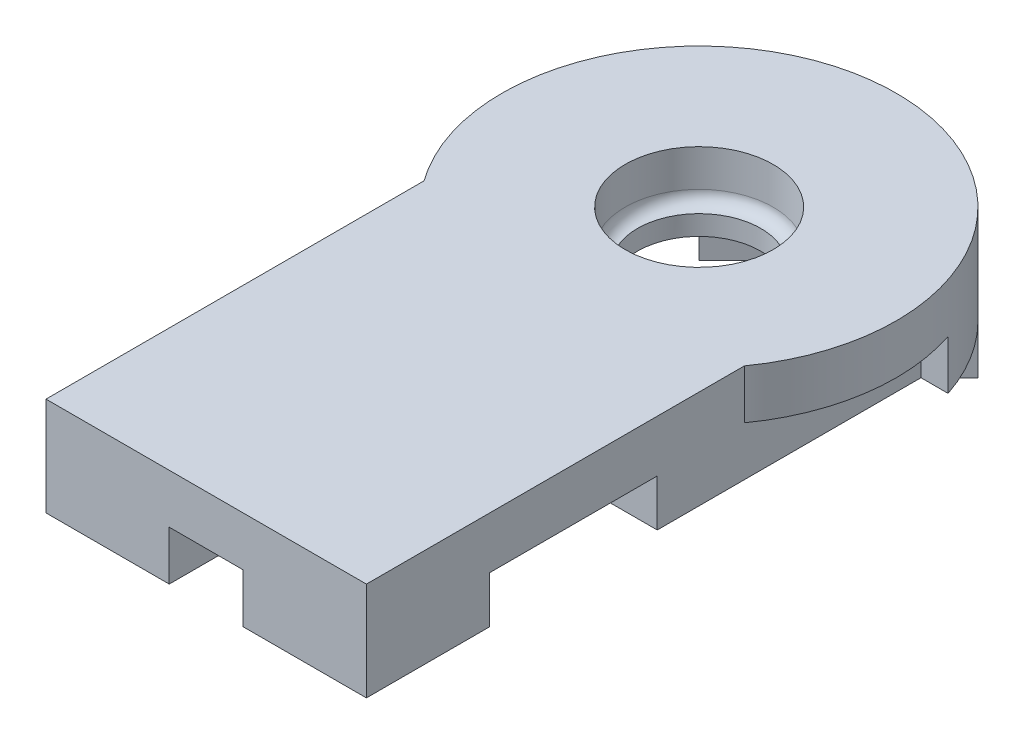
SolidWorks part; units mm, degrees
ref_plane "Front Plane" through (0, 0, 0) normal (0, 0, 1) x (1, 0, 0)
ref_plane "Top Plane" through (0, 0, 0) normal (0, 1, 0) x (1, 0, 0)
ref_plane "Right Plane" through (0, 0, 0) normal (1, 0, 0) x (0, 0, -1)
sketch "Sketch1" plane through (0, 0, 0) normal (0, 1, 0) x (1, 0, 0)
  line L0 (-996.0269, -20) -> (49003.9731, -20) construction
  line L3 (-6.5, -20) -> (6.5, -20)
  line L4 (6.5, -1010) -> (6.5, -4.6637) construction
  line L5 (-6.5, -1010) -> (-6.5, -4.6637) construction
  line L6 (6.5, -4.6637) -> (6.5, -20)
  line L7 (-6.5, -4.6637) -> (-6.5, -20)
  line L8 (-6.5, 4.6637) -> (-6.5, 48990) construction
  line L9 (6.5, 4.6637) -> (6.5, 48990) construction
  arc A0 (6.5, 4.6637) -> (-6.5, 4.6637) centre (0, 0) ccw
  arc A1 (-8, 0) -> (8, 0) centre (0, 0) ccw construction
  arc A2 (-6.5, 4.6637) -> (-8, 0) centre (0, 0) ccw construction
  arc A3 (8, 0) -> (6.5, 4.6637) centre (0, 0) ccw construction
  arc A4 (-6.5, 4.6637) -> (-6.5, -4.6637) centre (0, 0) ccw
  arc A5 (6.5, 4.6637) -> (6.5, -4.6637) centre (0, 0) cw
  dimension "D1" = 16
  dimension "D2" = 20
  dimension "D3" = 6.5
  dimension "D4" = 6.5
extrude "Boss-Extrude1" add sketch "Sketch1" against normal blind 4
sketch "Sketch2" plane through (0, 0, 0) normal (0, 1, 0) x (1, 0, 0)
  circle A1 centre (0, 0) radius 2.5
  dimension "D1" = 5
extrude "Cut-Extrude1" cut sketch "Sketch2" against normal through all
sketch "Sketch3" plane through (0, 0, 0) normal (0, 1, 0) x (1, 0, 0)
  circle A0 centre (0, 0) radius 3
extrude "Cut-Extrude2" cut sketch "Sketch3" against normal blind 2
sketch "Sketch4" plane through (0, -4, 0) normal (0, -1, 0) x (1, 0, 0)
  line L0 (0, 0) -> (0, -5.75) construction
  line L1 (2.5, -5.75) -> (-2.5, -5.75)
  line L2 (5.75, 0) -> (-5.75, 0) construction
  line L3 (5.75, -1000) -> (5.75, 49000) construction
  line L4 (-5.75, -1000) -> (-5.75, 49000) construction
  line L5 (2.5, -5.75) -> (5.75, -2.5)
  line L6 (5.75, -2.5) -> (5.75, 6.25)
  line L7 (-2.5, -5.75) -> (-5.75, -2.5)
  line L8 (-5.75, -2.5) -> (-5.75, 6.25)
  line L9 (-755.7679, 8.2) -> (49244.2321, 8.2) construction
  line L10 (2.9, 8.2) -> (2.1, 8.2) construction
  line L12 (-5.75, 6.25) -> (-4.4, 6.25)
  line L13 (-5.5, 6.5) -> (5.5, 6.5) construction
  line L14 (-4.4, 6.25) -> (-4.4, 8.2)
  line L15 (-6.5, 20) -> (6.5, 20) construction
  line L16 (-2.9, 6.8941) -> (-2.9, 8.2) construction
  line L18 (-6.5, 20) -> (6.5, 20) construction
  line L19 (6.5, 10) -> (6.5, 8.2)
  line L21 (-4.4, 6.25) -> (4.4, 6.25) construction
  line L22 (4.4, 6.25) -> (5.75, 6.25)
  line L23 (4.4, 8.2) -> (5.6604, 10) construction
  line L24 (-4.4, 8.2) -> (-5.6604, 10)
  line L25 (4.4, 8.2) -> (4.4, 20) construction
  line L26 (-4.4, 8.2) -> (-4.4, 20) construction
  line L27 (6.5, 11.1991) -> (6.5, 15)
  line L31 (-6.5, 11.1991) -> (-6.5, 15)
  line L33 (-6.5, 15) -> (-6.5, 20.6628) construction
  line L34 (-1005.75, -2.5) -> (48994.25, -2.5) construction
  line L35 (-999.9505, 10) -> (49000.0495, 10) construction
  line L36 (6.5, 11.1991) -> (6.5, 10)
  line L37 (-6.5, 15) -> (6.5, 15)
  line L39 (6.5, 15) -> (6.5, 20.6628) construction
  line L40 (6.5, 20) -> (6.5, 4.6637) construction
  line L41 (6.5, 10) -> (5.6604, 10) construction
  line L42 (5.75, 10.128) -> (6.5, 11.1991) construction
  line L43 (5.6604, 10) -> (5.75, 10.128) construction
  line L44 (-6.5, 11.1991) -> (-6.5, 10)
  line L45 (-6.5, 4.6637) -> (-6.5, 20) construction
  line L46 (-6.5, 10) -> (-5.6604, 10)
  line L47 (-5.6604, 10) -> (-5.75, 10.128) construction
  line L48 (-5.75, 10.128) -> (-6.5, 11.1991) construction
  line L49 (4.4, 8.2) -> (4.4, 6.25)
  line L50 (-6.5, 20) -> (6.5, 20) construction
  line L51 (6.5, 8.2) -> (4.4, 8.2)
  point P6 (0, -5.75)
  point P9 (0, 0)
  circle M8 centre (0, 0) radius 2.5
  line M20 (6.5, 4.6637) -> (6.5, 20)
  line M21 (-6.5, 20) -> (-6.5, 4.6637)
  dimension "D3" = 0.25
  dimension "D1" = 5.75
  dimension "D2" = 11.5
  dimension "D4" = 1.5
  dimension "D6" = 2.5
  dimension "D7" = 10
  dimension "D8" = 15
  dimension "D9" = 6.25
  dimension "D10" = 35
  dimension "D11" = 35
extrude "Cut-Extrude3" cut sketch "Sketch4" against normal blind 1.2 contours L46 L24 L14 L12 L8 L7 L1 L5 L6 L22 L49 L23 L41 L37 M21 M20 M8
sketch "Sketch6" plane through (0, -2.8, 0) normal (0, -1, 0) x (1, 0, 0)
  line L0 (6.5, 15) -> (6.5, 8.2)
  line L3 (4.4, 6.2) -> (-4.4, 6.2)
  line L4 (6.5, 8.2) -> (6.5, 15) construction
  line L5 (6.5, 15) -> (-6.5, 15)
  line L6 (-6.5, 15) -> (-6.5, 11.1991)
  line L7 (-5.6604, 10) -> (-4.4, 8.2)
  line L8 (-4.4, 8.2) -> (-4.4, 6.2)
  line L10 (6.5, 8.2) -> (4.4, 8.2)
  line L15 (-5.6604, 10) -> (-4.4, 8.2) construction
  line L16 (-6.5, 11.1991) -> (-6.5, 10)
  line L18 (-6.5, 10) -> (-5.6604, 10)
  line L19 (-6.5, 10) -> (-5.6604, 10) construction
  line L20 (-6.5, 11.1991) -> (-5.6604, 10) construction
  line L21 (4.4, 6.2) -> (4.4, 8.2)
  line L22 (4.4, 8.2) -> (4.4, 6.25) construction
  dimension "D1" = 2
extrude "Cut-Extrude5" cut sketch "Sketch6" against normal blind 0.7
sketch "Sketch7" plane through (0, 0, 20) normal (0, 0, 1) x (1, 0, 0)
  line L1 (-6.5, -4) -> (6.5, -4)
  line L2 (-6.5, -4) -> (-6.5, 0)
  line L3 (-6.5, 0) -> (6.5, 0)
  line L4 (6.5, -4) -> (6.5, 0)
extrude "Cut-Extrude6" [suppressed] cut sketch "Sketch7" against normal up to vertex
sketch "Sketch10" plane through (0, -4, 0) normal (0, -1, 0) x (1, 0, 0)
  line L0 (-6.5, 4.6637) -> (-6.5, -2.5)
  line L1 (6.5, 4.6637) -> (6.5, -2.5)
  line L2 (-1005.75, -2.5) -> (48994.25, -2.5) construction
  line L3 (-6.5, -2.5) -> (-7.5993, -2.5)
  line L4 (-6.5, -2.5) -> (-6.5, -4.6637) construction
  line L5 (6.5, -2.5) -> (7.5993, -2.5)
  line L6 (6.5, -2.5) -> (6.5, -4.6637) construction
  arc A0 (-6.5, 4.6637) -> (6.5, 4.6637) centre (0, 0) ccw construction
  arc A1 (-6.5, 4.6637) -> (-7.5993, -2.5) centre (0, 0) ccw
  arc A2 (6.5, 4.6637) -> (7.5993, -2.5) centre (0, 0) cw
  arc A3 (-7.5993, -2.5) -> (-6.5, -4.6637) centre (0, 0) ccw construction
  arc A4 (7.5993, -2.5) -> (6.5, -4.6637) centre (0, 0) cw construction
  dimension "D1" = 8
  dimension "D2" = 8
extrude "Cut-Extrude8" cut sketch "Sketch10" against normal blind 2
sketch "Sketch11" plane through (0, -4, 0) normal (0, -1, 0) x (1, 0, 0)
  line L0 (0, -1000) -> (0, 49000) construction
  line L1 (-0.75, -1003.313) -> (-0.75, 48996.687) construction
  line L2 (0.75, -1004.6428) -> (0.75, 48995.3572) construction
  line L3 (-0.75, -7.9648) -> (-0.75, -5.75)
  line L4 (-0.75, -5.75) -> (-2.5, -5.75)
  line L6 (0.75, -7.9648) -> (0.75, -5.75)
  line L7 (0.75, -5.75) -> (2.5, -5.75)
  line L9 (-2.5, -5.75) -> (2.5, -5.75) construction
  line L10 (0, 0) -> (35355.3391, -35355.3391) construction
  line L11 (2.5, -5.75) -> (5.75, -2.5) construction
  line L12 (0, 0) -> (-35355.3391, -35355.3391) construction
  line L13 (-5.75, -2.5) -> (-2.5, -5.75) construction
  line L14 (-2.5, -5.75) -> (-4.125, -4.125)
  line L15 (-4.125, -4.125) -> (-5.6569, -5.6569)
  line L16 (2.5, -5.75) -> (4.125, -4.125)
  line L17 (4.125, -4.125) -> (5.6569, -5.6569)
  arc A0 (-7.5993, -2.5) -> (7.5993, -2.5) centre (0, 0) ccw construction
  arc A1 (-5.6569, -5.6569) -> (-0.75, -7.9648) centre (0, 0) ccw
  arc A2 (5.6569, -5.6569) -> (0.75, -7.9648) centre (0, 0) cw
  point P27 (4.125, -4.125)
  point P32 (-4.125, -4.125)
  dimension "D1" = 0.75
  dimension "D2" = 0.75
extrude "Boss-Extrude3" add sketch "Sketch11" along normal blind 2
fillet "Fillet3" radius 0.5 1 edges at (0, -2, 3)
sketch "Sketch12" plane through (0, -4, 0) normal (0, -1, 0) x (1, 0, 0)
  line L0 (0, 20) -> (0, 15) construction
  line L1 (-6.5, 20) -> (6.5, 20) construction
  line L2 (6.5, 15) -> (-6.5, 15) construction
  line L3 (1.5, 15) -> (1.5, 20)
  line L4 (-1.5, 15) -> (-1.5, 20)
  line L5 (-1.5, 20) -> (1.5, 20)
  line L6 (0, 15) -> (-1.5, 15)
  line L7 (1.5, 15) -> (-1.5, 15)
  line L8 (1.5, 15) -> (0, 15) construction
  line M11 (6.5, 20) -> (-6.5, 20)
  dimension "D1" = 1.5
  dimension "D2" = 1.5
  dimension "D3" = 5
extrude "Cut-Extrude9" cut sketch "Sketch12" against normal blind 2 contours L7 L3 L4 M11
sketch "Sketch13" plane through (0, -2.1, 0) normal (0, -1, 0) x (1, 0, 0)
  line L0 (-6.5, 15) -> (-6.5, 10)
  line L1 (-6.5, 10) -> (-5.6604, 10)
  line L2 (-5.6604, 10) -> (-4.4, 8.2)
  line L3 (-4.4, 8.2) -> (-4.4, 15)
  line L4 (-6.5, 15) -> (-1.5, 15) construction
  line L5 (-4.4, 15) -> (-6.5, 15)
extrude "Boss-Extrude4" add sketch "Sketch13" along normal up to surface (1.9 mm away) up to face at (-5.6527, -4, 2.3304)
